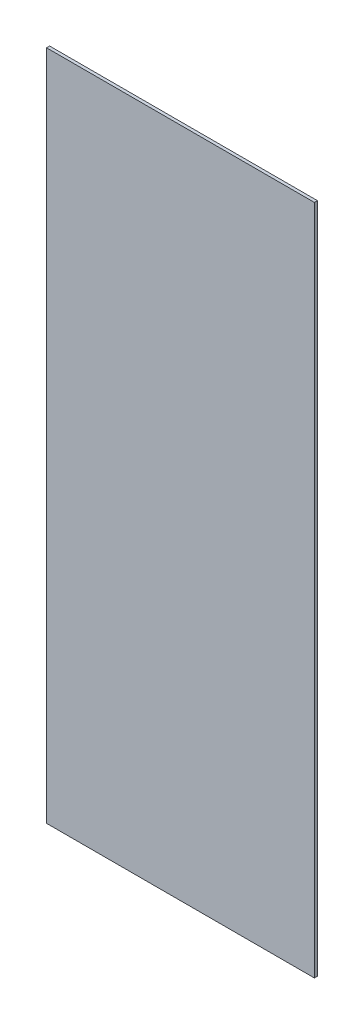
SolidWorks part; units mm, degrees
ref_plane "Спереди" through (0, 0, 0) normal (0, 0, 1) x (1, 0, 0)
ref_plane "Сверху" through (0, 0, 0) normal (0, 1, 0) x (1, 0, 0)
ref_plane "Справа" through (0, 0, 0) normal (1, 0, 0) x (0, 0, -1)
sketch "Эскиз1" plane through (0, 0, 0) normal (0, 0, 1) x (1, 0, 0)
  line L0 (0, -9) -> (0, 421) construction
  line L1 (524, -883) -> (0, -883)
  line L2 (524, -883) -> (524, 431)
  line L3 (524, 431) -> (0, 431)
  line L4 (0, -883) -> (0, 431)
  line L5 (518, 431) -> (0, 431) construction
  line L6 (524, -5) -> (524, 425) construction
  line L8 (518, -877) -> (524, -877) construction
  dimension "D1" = 6
extrude "Бобышка-Вытянуть1" add sketch "Эскиз1" against normal blind 6
equation "\"Толщина стенки\" = 6"
equation "\"Ширина груза\"= 420"
equation "\"Глубина груза\"= 490"
equation "\"Высота груза\"= 297"
equation "\"Ширина ячейки\"= \"Ширина груза\" + 10"
equation "\"Глубина ячейки\"= \"Глубина груза\" + 10"
equation "\"Высота ячейки\"= \"Высота груза\" + 10 + 13"
equation "\"Колво ячеек ширина\"= 2"
equation "\"Колво ячеек высота\"= 2"
equation "\"Крепление дверцы\"= 5"
equation "\"Ширина рейки\"= \"Толщина шестерни\""
equation "\"Высота рейки\"= 20"
equation "\"Высота пола\"= 20"
equation "\"Колво полозьев\"= 5"
equation "\"Отступ рейки\"= 20"
equation "\"Глубина каретки\"= \"Глубина ячейки\" + 30 + \"Мотор Y высота корпуса\" + 20"
equation "\"Длинна рейки\"= ( \"Ширина ячейки\" + \"Толщина стенки\" + \"Крепление дверцы\" ) * \"Колво ячеек ширина\" + \"Ширина ячейки выгрузки\" * \"Колво выгрузки\" + \"Толщина стенки\""
equation "\"Отступ шпильки\"= 26"
equation "\"Диаметр шпильки\"= 5"
equation "\"Длинна шпильки\"= ( \"Высота ячейки\" + \"Толщина стенки\" + \"Высота пола\" ) * \"Колво ячеек высота\" + ( \"Толщина стенки\" + \"Отступ рейки\" ) * 2 "
equation "\"Ширина пластины\"= 50  "
equation "\"Высота зона выгрузки\"= \"Высота ячейки\" * 2 + \"Толщина стенки\" * 2"
equation "\"Колво выгрузки\"= 1"
equation "\"Ширина ячейки выгрузки\"= \"Ширина ячейки\" + \"Толщина стенки\" + \"Отступ крепления мотора фиксации\"*2"
equation "\"Отступ крепления мотора фиксации\" = 30"
equation "\"Мотор X ширина корпуса\"= 42.3"
equation "\"Мотор X высота корпуса\"= 42.3"
equation "\"Мотор X длина корпуса\"= 40"
equation "\"Мотор X вылет вала\"= 19.8"
equation "\"Мотор Y ширина корпуса\"= 42.3"
equation "\"Мотор Y высота корпуса\"= 42.3"
equation "\"Мотор Y длина корпуса\"= 48"
equation "\"Мотор Y вылет вала\"= 30"
equation "\"Мотор Z ширина корпуса\"= 42"
equation "\"Мотор Z высота корпуса\"= 42"
equation "\"Мотор Z длина корпуса\"= 40"
equation "\"Мотор Z вылет вала\"= 23"
equation "\"Мотор диаметр вала ПРЕДВ\"= 5"
equation "\"Мотор шаг крепления ПРЕДВ\"= 31"
equation "\"Мотор диаметр отверстий ПРЕДВ\"= 3"
equation "\"Мотор глубина отверстий ПРЕДВ\"= 4.5"
equation "\"Мотор диаметр буртика ПРЕДВ\"= 22"
equation "\"Мотор высота буртика ПРЕДВ\"= 2"
equation "\"Мотор диаметр шкива ПРЕДВ\"= 16"
equation "\"Мотор длина шкива ПРЕДВ\"= 12"
equation "\"Мотор отступ шкива ПРЕДВ\"= 5"
equation "\"Мотор X шаг градусов\"= 1.8"
equation "\"Мотор Y шаг градусов\"= 1.8"
equation "\"Мотор Z шаг градусов\"= 1.8"
equation "\"Мотор Y диаметр ротора\"= 25.78"
equation "\"Толщина шестерни\"= 10"
equation "\"D1@Бобышка-Вытянуть1\"=\"Толщина стенки\""
equation "\"D1@Эскиз1\"=\"Толщина стенки\""
